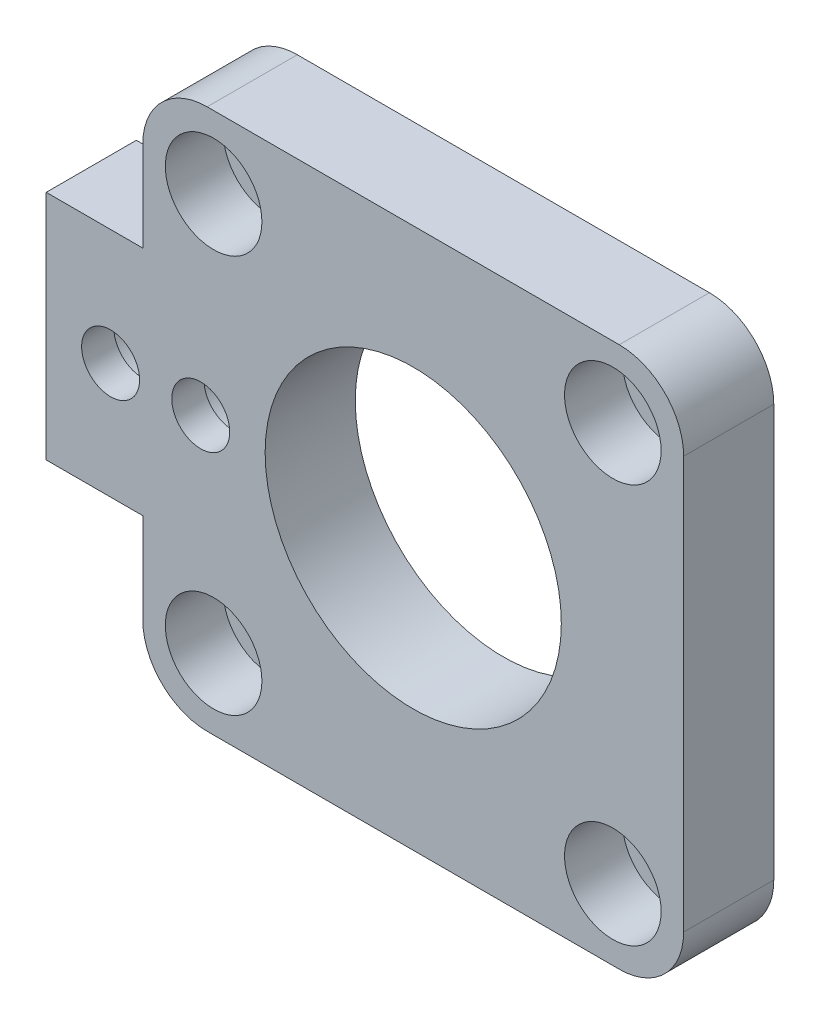
SolidWorks part; units mm, degrees
ref_plane "Plan de face" through (0, 0, 0) normal (0, 0, 1) x (1, 0, 0)
ref_plane "Plan de dessus" through (0, 0, 0) normal (0, 1, 0) x (1, 0, 0)
ref_plane "Plan de droite" through (0, 0, 0) normal (1, 0, 0) x (0, 0, -1)
sketch "Esquisse1" plane through (0, 0, 0) normal (0, 0, 1) x (1, 0, 0)
  line L1 (0, 0) -> (-42, 0)
  line L2 (0, 0) -> (0, -42)
  line L3 (0, -42) -> (-42, -42)
  line L4 (-42, 0) -> (-42, -42)
  line L5 (-42, -30) -> (-49.5, -30)
  line L6 (-42, -30) -> (-42, -12)
  line L7 (-42, -12) -> (-49.5, -12)
  line L8 (-49.5, -30) -> (-49.5, -12)
  circle A0 centre (-36.5, -5.611) radius 1.75
  circle A1 centre (-5.5, -5.5) radius 1.75
  circle A2 centre (-5.5, -36.5) radius 1.75
  circle A3 centre (-36.5, -36.5) radius 1.75
  circle A4 centre (-21, -21) radius 11.5
  dimension "D3" = 3.5
  dimension "D4" = 3.5
  dimension "D5" = 3.5
  dimension "D6" = 3.5
  dimension "D17" = 23
  dimension "D1" = 42
  dimension "D2" = 42
  dimension "D7" = 5.5
  dimension "D8" = 5.5
  dimension "D9" = 5.5
  dimension "D10" = 5.5
  dimension "D11" = 5.5
  dimension "D12" = 5.611
  dimension "D13" = 5.5
  dimension "D14" = 5.5
  dimension "D15" = 21
  dimension "D16" = 21
  dimension "D18" = 18
  dimension "D19" = 28.5
  dimension "D20" = 12
extrude "Boss.-Extru.1" add sketch "Esquisse1" along normal blind 7 contours L1 L4 L3 L2 A4 A3 A2 A1 A0 | L8 L5 L4 L7 region at (-0.594, -21, 0) region at (-45.75, -21, 0)
sketch "Esquisse9" plane through (0, 0, 7) normal (0, 0, 1) x (1, 0, 0)
  line L0 (-42, -30) -> (-49.5, -30) construction
  line L1 (-49.5, -30) -> (-49.5, -12) construction
  circle A0 centre (-44.5, -21) radius 2.25
  circle A1 centre (-37.5, -21) radius 2.25
  dimension "D1" = 4.5
  dimension "D2" = 4.5
  dimension "D3" = 9
  dimension "D4" = 9
  dimension "D5" = 5
  dimension "D6" = 12
extrude "Enlèv. mat.-Extru.2" cut sketch "Esquisse9" against normal blind 17 contours A1 | A0
sketch "Esquisse10" plane through (0, 0, 0) normal (0, 0, -1) x (-1, 0, 0)
  circle A0 centre (37.5, -21) radius 3.75
  circle A1 centre (44.5, -21) radius 3.75
  circle M1 centre (44.5, -21) radius 2.25
  circle M2 centre (37.5, -21) radius 2.25
  dimension "D1" = 7.5
  dimension "D2" = 7.5
extrude "Enlèv. mat.-Extru.3" cut sketch "Esquisse10" against normal blind 4.5 contours A1 A0 M2 | A0 A1 M1 | A0 A1 region at (-41, -21, 0) region at (-41.2895, -20.2963, 0) region at (-40.6457, -21, 0)
sketch "Esquisse11" plane through (0, 0, 7) normal (0, 0, 1) x (1, 0, 0)
  circle A0 centre (-36.5, -5.611) radius 3.75
  circle A1 centre (-5.5, -5.5) radius 3.75
  circle A2 centre (-5.5, -36.5) radius 3.75
  circle A3 centre (-36.5, -36.5) radius 3.75
  dimension "D1" = 7.5
  dimension "D2" = 7.5
  dimension "D3" = 7.5
  dimension "D4" = 7.5
extrude "Enlèv. mat.-Extru.4" cut sketch "Esquisse11" against normal blind 4.5
fillet "Congé1" radius 5 4 edges at (-42, 0, 3.5) (0, 0, 3.5) (0, -42, 3.5) (-42, -42, 3.5)
